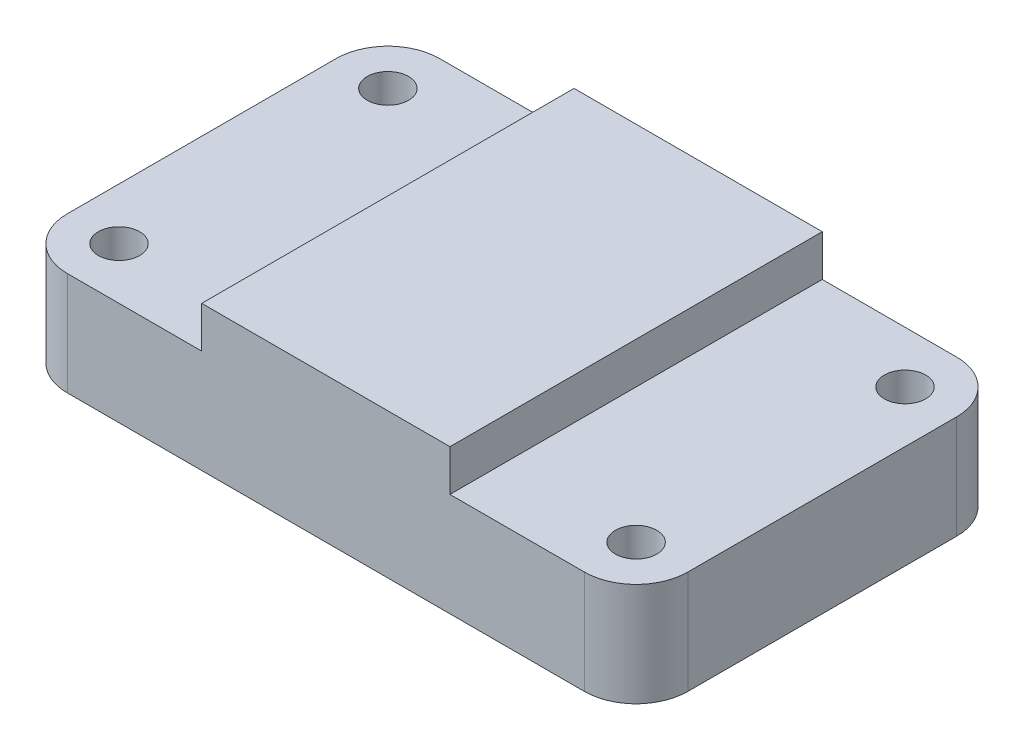
SolidWorks part; units mm, degrees
ref_plane "Front" through (0, 0, 0) normal (0, 0, 1) x (1, 0, 0)
ref_plane "Top" through (0, 0, 0) normal (0, 1, 0) x (1, 0, 0)
ref_plane "Right" through (0, 0, 0) normal (1, 0, 0) x (0, 0, -1)
sketch "Esquisse1" plane through (0, 0, 0) normal (0, 1, 0) x (1, 0, 0)
  line L0 (-60, 90) -> (-60, -90)
  line L1 (125, -90) -> (-125, -90)
  line L2 (150, -65) -> (150, 65)
  line L3 (125, 90) -> (-125, 90)
  line L4 (-150, -65) -> (-150, 65)
  line L5 (150, -90) -> (-150, 90) construction
  line L6 (150, 90) -> (-150, -90) construction
  line L7 (0, -90) -> (0, 90) construction
  line L8 (60, 90) -> (60, -90)
  arc A0 (-125, -90) -> (-150, -65) centre (-125, -65) cw
  arc A1 (125, -90) -> (150, -65) centre (125, -65) ccw
  arc A2 (150, 65) -> (125, 90) centre (125, 65) ccw
  arc A3 (-125, 90) -> (-150, 65) centre (-125, 65) ccw
  circle A4 centre (-125, 65) radius 10
  circle A5 centre (125, 65) radius 10
  circle A6 centre (125, -65) radius 10
  circle A7 centre (-125, -65) radius 10
  point P0 (0, 0)
  point P27 (0, 0)
  dimension "D3" = 25
  dimension "D4" = 20
  dimension "D1" = 180
  dimension "D2" = 300
  dimension "D5" = 60
extrude "Boss.-Extru.1" add sketch "Esquisse1" along normal blind 50 contours L3 A3 L4 A0 L1 L0 A7 A4 | L2 A2 L3 L8 L1 A1 A6 A5 region at (-103.4879, 0, 0) region at (103.4879, 0, 0)
extrude "Boss.-Extru.2" add sketch "Esquisse1<3>" along normal blind 70 contours L8 L3 L0 L1 region at (0, 0, 0)
sketch "Esquisse1<3>" plane through (0, 0, 0) normal (0, 1, 0) x (1, 0, 0) same geometry as "Esquisse1"
